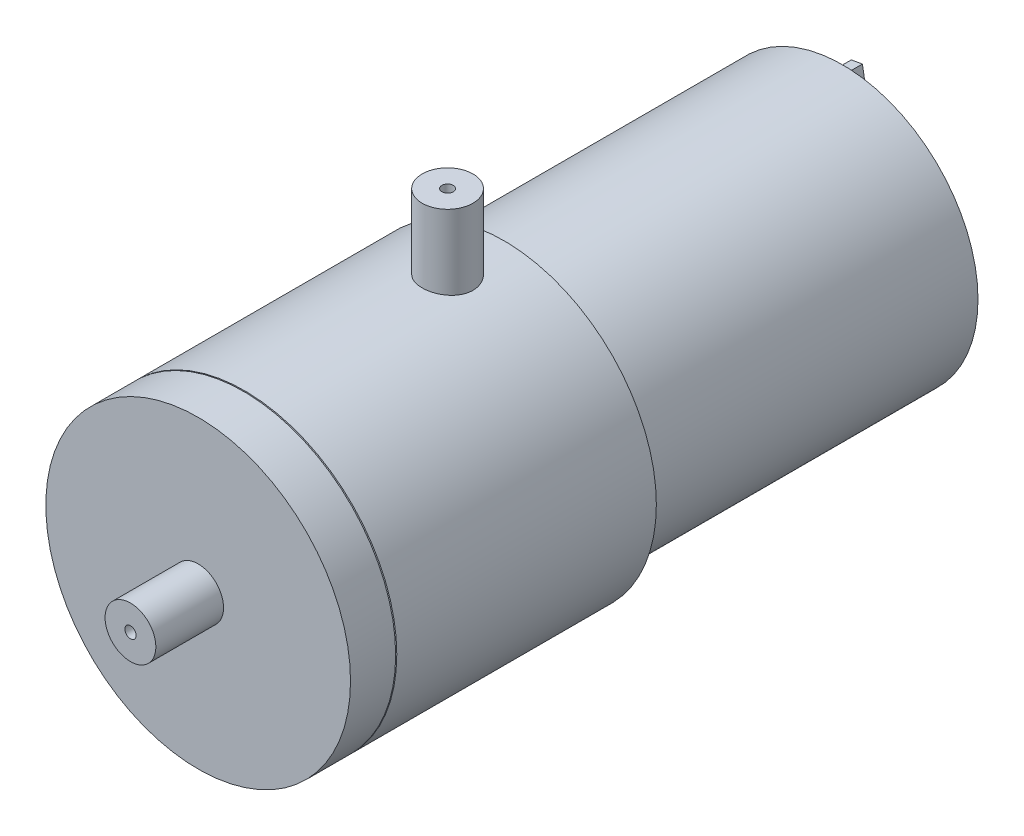
SolidWorks part; units mm, degrees
ref_plane "Front Plane" through (0, 0, 0) normal (0, 0, 1) x (1, 0, 0)
ref_plane "Top Plane" through (0, 0, 0) normal (0, 1, 0) x (1, 0, 0)
ref_plane "Right Plane" through (0, 0, 0) normal (1, 0, 0) x (0, 0, -1)
sketch "Sketch1" plane through (0, 0, 0) normal (0, 0, 1) x (1, 0, 0)
  circle A0 centre (0, 0) radius 13.5
extrude "Boss-Extrude1" add sketch "Sketch1" along normal blind 23
sketch "Sketch2" plane through (0, 0, 23) normal (0, 0, 1) x (1, 0, 0)
  circle A0 centre (0, 0) radius 12.5
extrude "Boss-Extrude2" add sketch "Sketch2" along normal blind 0.1
sketch "Sketch3" plane through (0, 0, 23.1) normal (0, 0, 1) x (1, 0, 0)
  circle A0 centre (0, 0) radius 13.5
extrude "Boss-Extrude3" add sketch "Sketch3" along normal blind 4
sketch "Sketch4" plane through (0, 0, 0) normal (0, 0, -1) x (-1, 0, 0)
  circle A0 centre (0, 0) radius 12
extrude "Boss-Extrude4" add sketch "Sketch4" along normal blind 30
sketch "Sketch5" plane through (0, 0, -30) normal (0, 0, -1) x (-1, 0, 0)
  circle A0 centre (0, 0) radius 11.5
  circle A2 centre (0, 0) radius 3
  dimension "D1" = 6
  dimension "D3" = 23
extrude "Cut-Extrude1" cut sketch "Sketch5" against normal blind 2 contours A0 A2 region at (11.1747, 0, -30)
sketch "Sketch6" plane through (0, 0, 27.1) normal (0, 0, 1) x (1, 0, 0)
  circle A0 centre (0, 0) radius 2.25
  circle A1 centre (0, 0) radius 0.5
extrude "Boss-Extrude5" add sketch "Sketch6" along normal blind 6
sketch "Sketch7" plane through (0, 0, 0) normal (0, 1, 0) x (1, 0, 0)
  line L0 (13.5, 0) -> (-13.5, 0) construction
  circle A0 centre (0, -5) radius 2.25
  circle A1 centre (0, -5) radius 0.5
  dimension "D1" = 5
extrude "Boss-Extrude6" add sketch "Sketch7" along normal blind 20
sketch "Sketch8" plane through (0, 0, -28) normal (0, 0, -1) x (-1, 0, 0)
  line L0 (0, 0) -> (1.3892, 7.8785) construction
  line L1 (0.5495, 5.9957) -> (1.2441, 9.9349)
  line L2 (0.5495, 5.9957) -> (1.5343, 5.822)
  line L3 (1.2441, 9.9349) -> (2.2289, 9.7613)
  line L4 (1.5343, 5.822) -> (2.2289, 9.7613)
  line L5 (0.5495, 5.9957) -> (2.2289, 9.7613) construction
  line L6 (1.2441, 9.9349) -> (1.5343, 5.822) construction
  line L7 (0, 0) -> (0, 5.8618) construction
  line L20 (0, 0) -> (1.7734, -0.3127) construction
  line L21 (-2.2289, -9.7613) -> (-1.2441, -9.9349)
  line L22 (-0.5495, -5.9957) -> (-1.2441, -9.9349)
  line L23 (-1.5343, -5.822) -> (-2.2289, -9.7613)
  line L24 (-1.5343, -5.822) -> (-0.5495, -5.9957)
  point P23 (0, 0)
  dimension "D1" = 4
  dimension "D2" = 1
  dimension "D3" = 8
  dimension "D4" = 10
extrude "Boss-Extrude7" add sketch "Sketch8" along normal blind 5
sketch "Sketch9" plane through (0, 0, -30) normal (0, 0, -1) x (-1, 0, 0)
  line L1 (-0.25, 0.25) -> (0.25, 0.25)
  line L2 (-0.25, 0.25) -> (-0.25, -0.25)
  line L3 (-0.25, -0.25) -> (0.25, -0.25)
  line L4 (0.25, 0.25) -> (0.25, -0.25)
  line L5 (-0.25, 0.25) -> (0.25, -0.25) construction
  line L6 (-0.25, -0.25) -> (0.25, 0.25) construction
  point P0 (0, 0)
  dimension "D1" = 0.5
  dimension "D2" = 0.5
extrude "Cut-Extrude2" cut sketch "Sketch9" against normal blind 0.5
